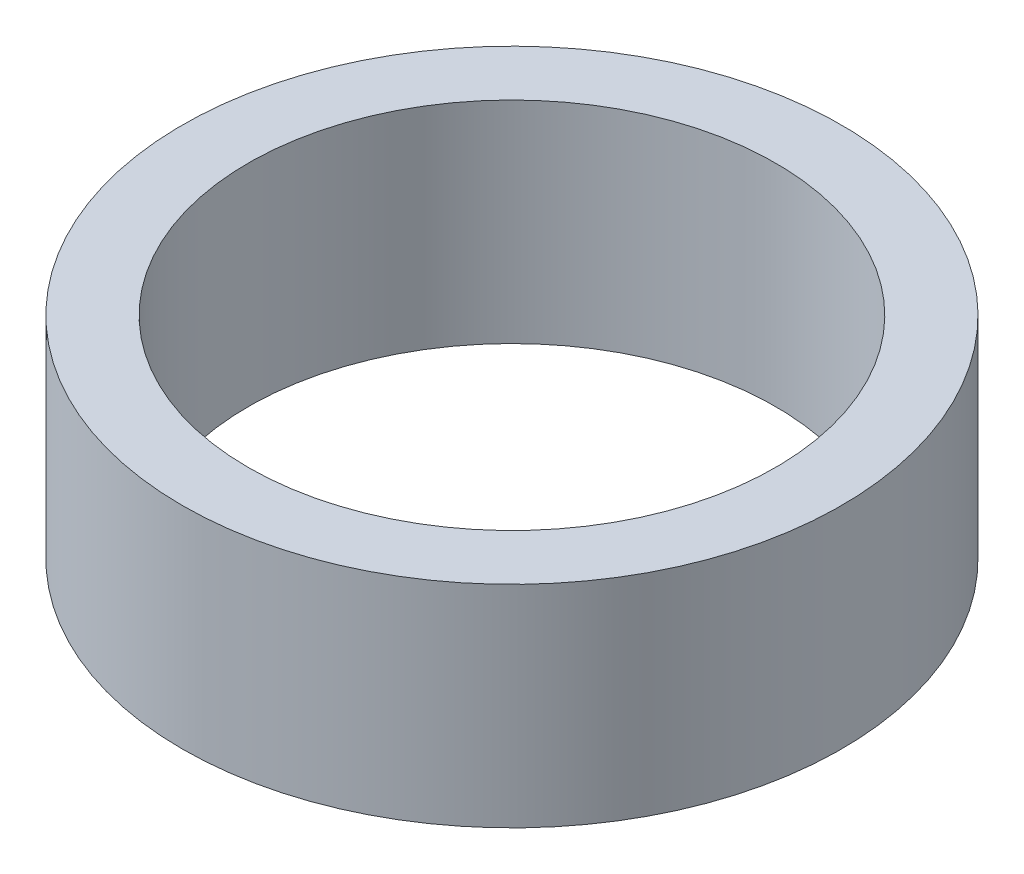
SolidWorks part; units mm, degrees
ref_plane "Front Plane" through (0, 0, 0) normal (0, 0, 1) x (1, 0, 0)
ref_plane "Top Plane" through (0, 0, 0) normal (0, 1, 0) x (1, 0, 0)
ref_plane "Right Plane" through (0, 0, 0) normal (1, 0, 0) x (0, 0, -1)
sketch "Sketch1" plane through (0, 0, 0) normal (0, 1, 0) x (1, 0, 0)
  circle A0 centre (0, 0) radius 37.5
  dimension "FLANGE_OD" = 75
extrude "Boss-Extrude1" add sketch "Sketch1" along normal blind 24
sketch "Sketch2" plane through (0, 0, 0) normal (0, 1, 0) x (1, 0, 0)
  circle A0 centre (0, 0) radius 30
  dimension "BORE_D" = 60
extrude "Cut-Extrude1" cut sketch "Sketch2" along normal through all
sketch "Sketch3" plane through (0, 24, 0) normal (0, 1, 0) x (1, 0, 0)
  circle A0 centre (0, 0) radius 16.978 construction
  circle A1 centre (-16.978, 0) radius 1.5
  dimension "BOLT_D" = 3
  dimension "BOLT_PCD" = 33.9559
extrude "Cut-Extrude2" cut sketch "Sketch3" against normal blind 18.4548 rebuild error yes
pattern_circular "CirPattern1" count 5 over 360 rebuild error yes
